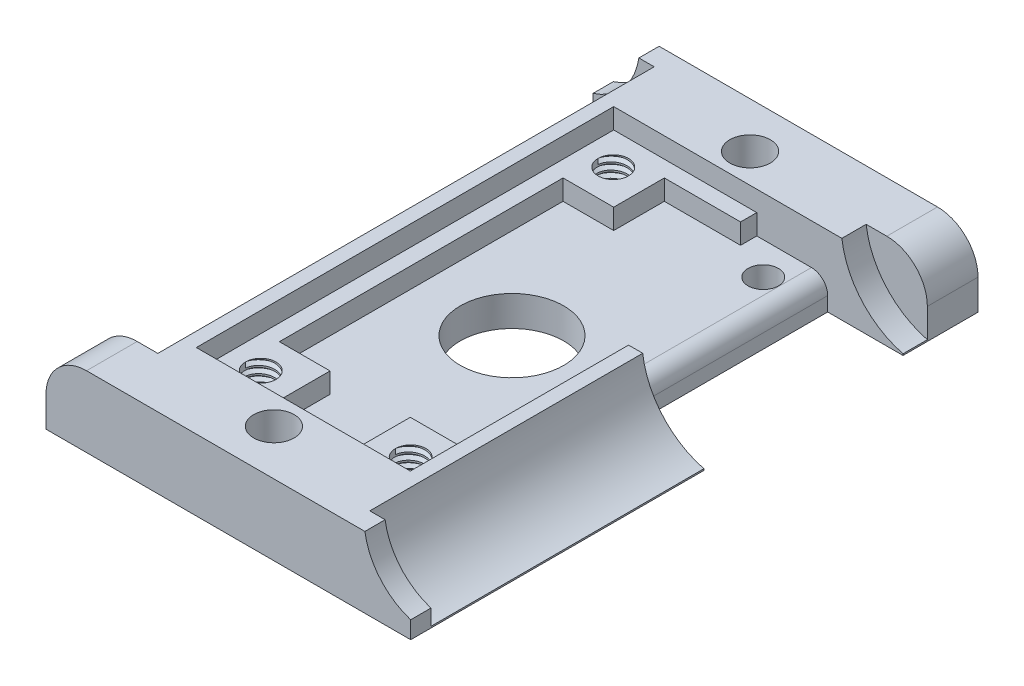
SolidWorks part; units mm, degrees
ref_plane "Front Plane" through (0, 0, 0) normal (0, 0, 1) x (1, 0, 0)
ref_plane "Top Plane" through (0, 0, 0) normal (0, 1, 0) x (1, 0, 0)
ref_plane "Right Plane" through (0, 0, 0) normal (1, 0, 0) x (0, 0, -1)
sketch "Sketch1" plane through (0, 0, 0) normal (0, 1, 0) x (1, 0, 0)
  line L1 (13.1473, -19.7747) -> (-4.8527, -19.7747)
  line L2 (13.1473, -19.7747) -> (13.1473, -47.7747)
  line L3 (13.1473, -47.7747) -> (-4.8527, -47.7747)
  line L4 (-4.8527, -19.7747) -> (-4.8527, -47.7747)
  dimension "D1" = 18
  dimension "D2" = 28
extrude "Boss-Extrude1" add sketch "Sketch1" along normal blind 4
sketch "Sketch2" plane through (0, 0, 19.7747) normal (0, 0, -1) x (-1, 0, 0)
  circle A0 centre (-14.1473, 4) radius 4.05
  circle A1 centre (5.8527, 4) radius 4.05
  dimension "D1" = 8.1
  dimension "D2" = 8.1
extrude "Cut-Extrude1" cut sketch "Sketch2" against normal through all
sketch "Sketch5" plane through (0, 4, 0) normal (0, 1, 0) x (1, 0, 0)
  line L0 (13.1473, -19.7747) -> (13.1473, -47.7747) construction
  line L1 (10.0973, -19.7747) -> (13.1473, -19.7747)
  line L2 (10.0973, -19.7747) -> (10.0973, -22.2747)
  line L3 (10.0973, -22.2747) -> (13.1473, -22.2747)
  line L4 (13.1473, -19.7747) -> (13.1473, -22.2747)
  line L5 (-4.8527, -47.7747) -> (-4.8527, -19.7747) construction
  line L6 (-1.8027, -47.7747) -> (-4.8527, -47.7747)
  line L7 (-1.8027, -47.7747) -> (-1.8027, -45.2747)
  line L8 (-1.8027, -45.2747) -> (-4.8527, -45.2747)
  line L9 (-4.8527, -47.7747) -> (-4.8527, -45.2747)
  dimension "D1" = 2.5
  dimension "D2" = 2.5
extrude "Boss-Extrude2" add sketch "Sketch5" against normal up to surface (4 mm away) up to face at (4.1473, 0, 33.7747)
sketch "Sketch6" plane through (0, 4, 0) normal (0, 1, 0) x (1, 0, 0)
  line L0 (13.1473, -22.2747) -> (13.1473, -47.7747) construction
  line L1 (10.0973, -47.7747) -> (13.1473, -47.7747)
  line L2 (10.0973, -47.7747) -> (10.0973, -46.7747)
  line L3 (10.0973, -46.7747) -> (13.1473, -46.7747)
  line L4 (13.1473, -47.7747) -> (13.1473, -46.7747)
  line L5 (-4.8527, -45.2747) -> (-4.8527, -19.7747) construction
  line L6 (-1.8027, -19.7747) -> (-4.8527, -19.7747)
  line L7 (-1.8027, -19.7747) -> (-1.8027, -20.7747)
  line L8 (-1.8027, -20.7747) -> (-4.8527, -20.7747)
  line L9 (-4.8527, -19.7747) -> (-4.8527, -20.7747)
  dimension "D1" = 1
  dimension "D2" = 1
extrude "Boss-Extrude3" add sketch "Sketch6" against normal up to surface (4 mm away) up to face at (4.1473, 0, 33.7747)
sketch "Sketch7" plane through (0, 0, 47.7747) normal (0, 0, 1) x (1, 0, 0)
  circle A0 centre (14.1473, 4) radius 3.3
  dimension "D1" = 6.6
extrude "Cut-Extrude4" cut sketch "Sketch7" against normal blind 2
sketch "Sketch8" plane through (0, 0, 19.7747) normal (0, 0, -1) x (-1, 0, 0)
  circle A0 centre (5.8527, 4) radius 3.3
  dimension "D1" = 6.6
extrude "Cut-Extrude5" cut sketch "Sketch8" against normal blind 2
sketch "Sketch9" plane through (0, 4, 0) normal (0, 1, 0) x (1, 0, 0)
  circle A0 centre (4.1473, -45.5247) radius 1
  circle A1 centre (4.1473, -22.0247) radius 1
  dimension "D1" = 2
  dimension "D2" = 2
extrude "Cut-Extrude6" cut sketch "Sketch9" against normal through all
sketch "Sketch10" plane through (0, 0, 0) normal (0, -1, 0) x (1, 0, 0)
  circle A0 centre (4.1473, 45.5247) radius 1.6
  circle A1 centre (4.1473, 22.0247) radius 1.6
  dimension "D1" = 3.2
  dimension "D2" = 3.2
extrude "Cut-Extrude7" cut sketch "Sketch10" against normal blind 1.5
sketch "Sketch11" plane through (0, 0, 19.7747) normal (0, 0, -1) x (-1, 0, 0)
  line L0 (4.8527, 0.0754) -> (4.8527, 4) construction
  line L1 (-13.1473, 4) -> (4.8527, 4)
  line L2 (-13.1473, 4) -> (-13.1473, 3.5)
  line L3 (-13.1473, 3.5) -> (4.8527, 3.5)
  line L4 (4.8527, 4) -> (4.8527, 3.5)
  dimension "D1" = 0.5
extrude "Cut-Extrude8" cut sketch "Sketch11" against normal through all
fillet "Fillet2" radius 2 2 edges at (-4.8527, 3.5, 46.5247) (13.1473, 3.5, 21.0247)
sketch "Sketch12" plane through (0, 3.5, 0) normal (0, 1, 0) x (1, 0, 0)
  line L0 (10.8854, -47.7747) -> (-2.8527, -47.7747) construction
  line L1 (8.6283, -43.2747) -> (-0.3337, -43.2747)
  line L2 (8.6283, -43.2747) -> (8.6283, -24.2747)
  line L3 (8.6283, -24.2747) -> (-0.3337, -24.2747)
  line L4 (-0.3337, -43.2747) -> (-0.3337, -24.2747)
  line L5 (11.1473, -19.7747) -> (-2.5908, -19.7747) construction
  line L6 (-1.8337, -45.2747) -> (-1.8337, -20.7747) construction
  line L7 (10.1283, -22.2747) -> (10.1283, -46.7747) construction
  dimension "D1" = 4.5
  dimension "D2" = 4.5
  dimension "D3" = 1.5
  dimension "D4" = 1.5
extrude "Cut-Extrude9" cut sketch "Sketch12" against normal blind 2
sketch "Sketch13" plane through (0, 1.5, 0) normal (0, 1, 0) x (1, 0, 0)
  circle A0 centre (4.1473, -33.7747) radius 2.55
  dimension "D1" = 5.1
extrude "Cut-Extrude10" cut sketch "Sketch13" against normal blind 2
sketch "Sketch15" plane through (0, 3.5, 0) normal (0, 1, 0) x (1, 0, 0)
  line L0 (10.8854, -47.7747) -> (-2.8527, -47.7747) construction
  line L1 (9.4283, -44.0747) -> (-1.1337, -44.0747)
  line L2 (9.4283, -44.0747) -> (9.4283, -23.4747)
  line L3 (9.4283, -23.4747) -> (-1.1337, -23.4747)
  line L4 (-1.1337, -44.0747) -> (-1.1337, -23.4747)
  line L5 (-1.8337, -45.2747) -> (-1.8337, -20.7747) construction
  line L6 (10.1283, -22.2747) -> (10.1283, -46.7747) construction
  line L7 (11.1473, -19.7747) -> (-2.5908, -19.7747) construction
  dimension "D1" = 3.7
  dimension "D2" = 0.7
  dimension "D3" = 0.7
  dimension "D4" = 3.7
extrude "Cut-Extrude11" cut sketch "Sketch15" against normal blind 1
sketch "Sketch16" plane through (0, 2.5, 0) normal (0, 1, 0) x (1, 0, 0)
  line L1 (8.6283, -43.2747) -> (6.1283, -43.2747)
  line L2 (8.6283, -43.2747) -> (8.6283, -40.7747)
  line L3 (8.6283, -40.7747) -> (6.1283, -40.7747)
  line L4 (6.1283, -43.2747) -> (6.1283, -40.7747)
  line L5 (-0.3337, -43.2747) -> (2.1663, -43.2747)
  line L6 (-0.3337, -43.2747) -> (-0.3337, -40.7747)
  line L7 (-0.3337, -40.7747) -> (2.1663, -40.7747)
  line L8 (2.1663, -43.2747) -> (2.1663, -40.7747)
  line L9 (-0.3337, -24.2747) -> (2.1663, -24.2747)
  line L10 (-0.3337, -24.2747) -> (-0.3337, -26.7747)
  line L11 (-0.3337, -26.7747) -> (2.1663, -26.7747)
  line L12 (2.1663, -24.2747) -> (2.1663, -26.7747)
  line L13 (8.6283, -24.2747) -> (6.1283, -24.2747)
  line L14 (8.6283, -24.2747) -> (8.6283, -26.7747)
  line L15 (8.6283, -26.7747) -> (6.1283, -26.7747)
  line L16 (6.1283, -24.2747) -> (6.1283, -26.7747)
  dimension "D1" = 2.5
  dimension "D2" = 2.5
  dimension "D3" = 2.5
  dimension "D4" = 2.5
  dimension "D5" = 2.5
  dimension "D6" = 2.5
  dimension "D7" = 2.5
  dimension "D8" = 2.5
extrude "Boss-Extrude4" add sketch "Sketch16" against normal up to surface (1 mm away) up to face at (4.1473, 1.5, 36.3247)
sketch "Sketch17" plane through (0, 2.5, 0) normal (0, 1, 0) x (1, 0, 0)
  line L0 (6.1283, -24.2747) -> (6.1283, -26.7747) construction
  line L1 (6.1283, -26.7747) -> (8.6283, -26.7747) construction
  line L2 (-0.3337, -26.7747) -> (2.1663, -26.7747) construction
  line L3 (2.1663, -26.7747) -> (2.1663, -24.2747) construction
  line L4 (6.1283, -40.7747) -> (6.1283, -43.2747) construction
  line L5 (8.6283, -40.7747) -> (6.1283, -40.7747) construction
  line L6 (-1.1337, -44.0747) -> (9.4283, -44.0747) construction
  line L7 (-1.1337, -23.4747) -> (-1.1337, -44.0747) construction
  circle A0 centre (7.8483, -42.4747) radius 0.75
  circle A1 centre (0.4463, -42.4747) radius 0.75
  circle A2 centre (0.4463, -25.0747) radius 0.75
  circle A3 centre (7.8483, -25.0747) radius 0.75
  dimension "D1" = 1.5
  dimension "D2" = 1.72
  dimension "D3" = 1.7
  dimension "D4" = 1.7
  dimension "D5" = 1.5
  dimension "D6" = 1.72
  dimension "D7" = 1.5
  dimension "D8" = 1.72
  dimension "D9" = 1.7
  dimension "D10" = 1.5
  dimension "D11" = 1.6
  dimension "D12" = 1.58
extrude "Cut-Extrude12" cut sketch "Sketch17" against normal through all
thread "Thread1" pitch 0.35 method cut profile "Thread Profile1" start angle 0, offset 0, length 10, pitch 0.35, diameter 1.5
ref_plane "Plane1" through (7.0983, 2.5, 42.4747) normal (0, 0, 1) x (-1, 0, 0)
sketch "Thread Profile1" plane through (7.0983, 2.5, 42.4747) normal (0, 0, 1) x (-1, 0, 0)
  line L0 (0, 0) -> (0, 0.35) construction
  line L1 (0, 0) -> (0.1894, 0.1094)
  line L2 (0.1894, 0.1094) -> (0.1894, 0.1531)
  line L3 (0.1894, 0.1531) -> (0, 0.2625)
  line L4 (0.1894, 0.1312) -> (0, 0.1312) construction
  line L11 (0, 0) -> (0, 0.2625)
  point P2 (0, 0)
  dimension "Pitch" = 0.35
  dimension "Profile_Angle" = 60
  dimension "Profile_Land" = 0.0437
  dimension "Profile_Height" = 0.1894
sketch "Sketch18" plane through (0, 3.5, 0) normal (0, 1, 0) x (1, 0, 0)
  line L0 (13.1473, -22.2747) -> (13.1473, -46.7747) construction
  line L1 (9.4283, -23.4747) -> (13.1473, -23.4747)
  line L2 (9.4283, -23.4747) -> (9.4283, -33.3024)
  line L3 (9.4283, -33.3024) -> (13.1473, -33.3024)
  line L4 (13.1473, -23.4747) -> (13.1473, -33.3024)
extrude "Cut-Extrude13" cut sketch "Sketch18" against normal through all
sketch "Sketch19" plane through (0, 2.5, 0) normal (0, 1, 0) x (1, 0, 0)
  line L1 (9.4283, -23.4747) -> (5.9283, -23.4747)
  line L2 (9.4283, -23.4747) -> (9.4283, -33.3024)
  line L3 (9.4283, -33.3024) -> (5.9283, -33.3024)
  line L4 (5.9283, -23.4747) -> (5.9283, -33.3024)
  dimension "D1" = 3.5
extrude "Cut-Extrude14" cut sketch "Sketch19" against normal blind 1
fillet "Fillet3" radius 0.8 1 edges at (9.4283, 1.5, 28.3885)
thread "Thread5" pitch 0.35 method cut profile "Thread Profile6" start angle 0, offset 0, length 10, pitch 0.35, diameter 1.5
ref_plane "Plane6" through (-0.3037, 2.5, 42.4747) normal (0, 0, 1) x (-1, 0, 0)
sketch "Thread Profile6" plane through (-0.3037, 2.5, 42.4747) normal (0, 0, 1) x (-1, 0, 0)
  line L0 (0, 0) -> (0, 0.35) construction
  line L1 (0, 0) -> (0.1894, 0.1094)
  line L2 (0.1894, 0.1094) -> (0.1894, 0.1531)
  line L3 (0.1894, 0.1531) -> (0, 0.2625)
  line L4 (0.1894, 0.1312) -> (0, 0.1312) construction
  line L11 (0, 0) -> (0, 0.2625)
  point P2 (0, 0)
  dimension "Pitch" = 0.35
  dimension "Profile_Angle" = 60
  dimension "Profile_Land" = 0.0437
  dimension "Profile_Height" = 0.1894
thread "Thread6" pitch 0.35 method cut profile "Thread Profile7" start angle 0, offset 0, length 10, pitch 0.35, diameter 1.5
ref_plane "Plane7" through (-0.3037, 2.5, 25.0747) normal (0, 0, 1) x (-1, 0, 0)
sketch "Thread Profile7" plane through (-0.3037, 2.5, 25.0747) normal (0, 0, 1) x (-1, 0, 0)
  line L0 (0, 0) -> (0, 0.35) construction
  line L1 (0, 0) -> (0.1894, 0.1094)
  line L2 (0.1894, 0.1094) -> (0.1894, 0.1531)
  line L3 (0.1894, 0.1531) -> (0, 0.2625)
  line L4 (0.1894, 0.1312) -> (0, 0.1312) construction
  line L11 (0, 0) -> (0, 0.2625)
  point P2 (0, 0)
  dimension "Pitch" = 0.35
  dimension "Profile_Angle" = 60
  dimension "Profile_Land" = 0.0437
  dimension "Profile_Height" = 0.1894
